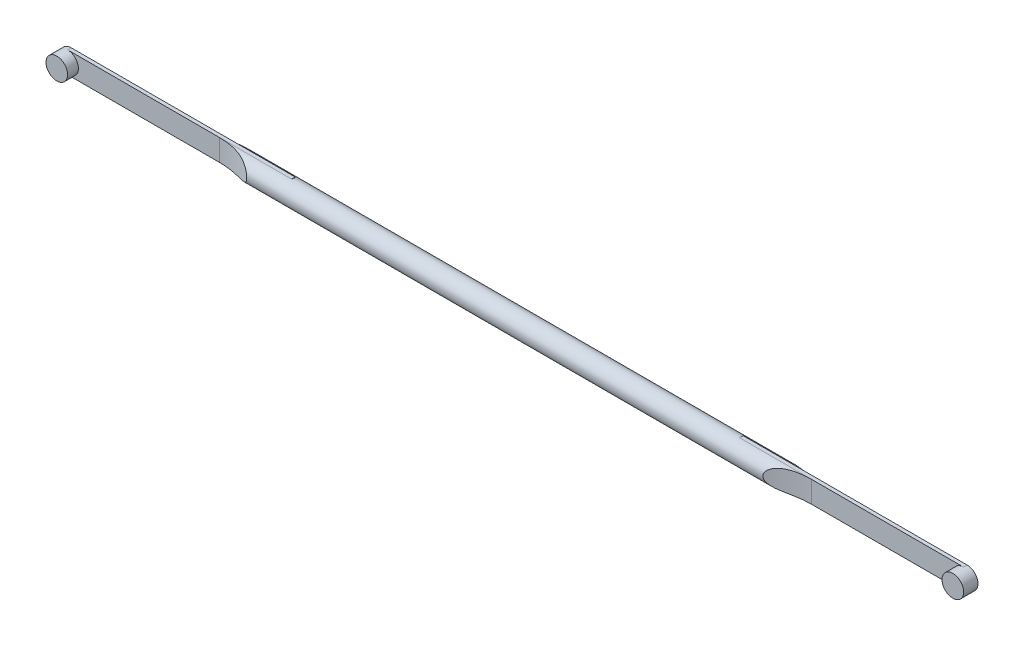
SolidWorks part; units mm, degrees
ref_plane "Front Plane" through (0, 0, 0) normal (0, 0, 1) x (1, 0, 0)
ref_plane "Top Plane" through (0, 0, 0) normal (0, 1, 0) x (1, 0, 0)
ref_plane "Right Plane" through (0, 0, 0) normal (1, 0, 0) x (0, 0, -1)
sketch "Sketch1" plane through (0, 0, 0) normal (0, 0, 1) x (1, 0, 0)
  line L0 (-62.25, 0) -> (62.25, 0)
  line L1 (0, 3) -> (0, 0)
  line L4 (62.25, 3) -> (0, 3)
  line L6 (-62.25, 3) -> (-62.25, 0)
  line L7 (-62.25, 3) -> (0, 3)
  line L9 (62.25, 3) -> (62.25, 0)
  point P0 (0, 0)
  point P3 (0, 0)
  dimension "D2" = 124.5
  dimension "D1" = 3
revolve "Revolve2" add sketch "Sketch1" angle 360 about L0
sketch "Sketch8" plane through (0, 0, 0) normal (0, 0, 1) x (1, 0, 0)
  line L0 (-62.25, 3) -> (-62.25, -3)
  line L1 (-124.5, 3) -> (-124.5, -3)
  line L2 (-62.25, 3) -> (-124.5, 3)
  line L3 (-62.25, -3) -> (-124.5, -3)
  line L4 (0, -3.3) -> (0, 3.3) construction
  line L5 (62.25, 3) -> (62.25, -3)
  line L6 (62.25, -3) -> (124.5, -3)
  line L7 (62.25, 3) -> (124.5, 3)
  line L8 (124.5, 3) -> (124.5, -3)
  dimension "D2" = 62.25
  dimension "D3" = 6
extrude "Boss-Extrude1" add sketch "Sketch8" against normal blind 1 contours L3 L0 L2 | L7 L5 L6 region at (-93.375, 0, 0) region at (93.375, 0, 0)
fillet "Fillet3" radius 20 4 edges at (62.25, 0, 0) (62.25, 0, -1) (-62.25, 0, 0) (-62.25, 0, -1)
sketch "Sketch20" plane through (0, 0, -1) normal (0, 0, -1) x (-1, 0, 0)
  line L0 (124.5, 3) -> (124.5, -3) construction
  line L1 (-124.5, 3) -> (-124.5, -3) construction
  circle A0 centre (124.5, 0) radius 3
  circle A1 centre (-124.5, 0) radius 3
extrude "Cut-Extrude2" cut sketch "Sketch20" against normal through all both and the other way through all
sketch "Sketch22" plane through (0, 0, -1) normal (0, 0, -1) x (-1, 0, 0)
  line L2 (124.5, 3) -> (124.5, -3)
  arc A2 (124.5, -3) -> (124.5, 3) centre (124.5, 0) ccw
extrude "Boss-Extrude2" add sketch "Sketch20<3>" against normal through all and the other way blind 4 contours A0
sketch "Sketch20<3>" plane through (0, 0, -1) normal (0, 0, -1) x (-1, 0, 0) same geometry as "Sketch20"
revolve "Cut-Revolve3" cut sketch "Sketch22" angle 360 about L2
sketch "Sketch25" plane through (0, 0, -1) normal (0, 0, -1) x (-1, 0, 0)
  line L0 (-124.5, 3) -> (-124.5, -3)
  arc A0 (-124.5, -3) -> (-124.5, 3) centre (-124.5, 0) ccw
mirror "Mirror3" about plane through (0, 0, 0) normal (1, 0, 0) of "Boss-Extrude2"
revolve "Cut-Revolve4" cut sketch "Sketch25" angle 360 about L0 body kept at (82.239, 3, 0)
